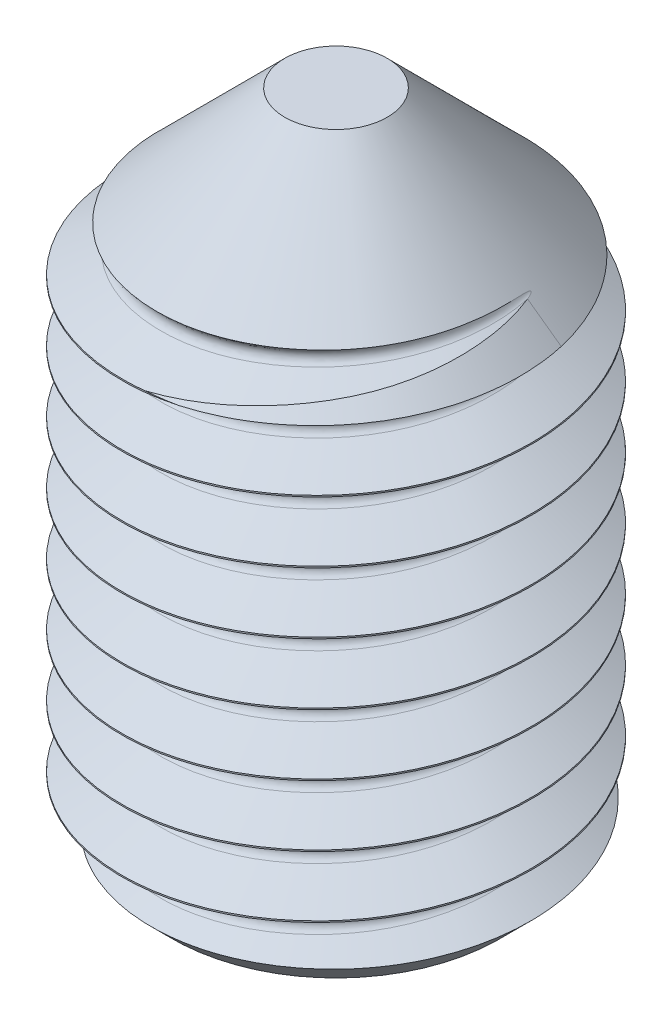
SolidWorks part; units mm, degrees
ref_plane "Front Plane" through (0, 0, 0) normal (0, 0, 1) x (1, 0, 0)
ref_plane "Top Plane" through (0, 0, 0) normal (0, 1, 0) x (1, 0, 0)
ref_plane "Right Plane" through (0, 0, 0) normal (1, 0, 0) x (0, 0, -1)
sketch "Sketch1" plane through (0, 0, 0) normal (0, 1, 0) x (1, 0, 0)
  circle A0 centre (0, 0) radius 5
  dimension "D1" = 10
extrude "Boss-Extrude1" add sketch "Sketch1" along normal mid plane 16
sketch "Sketch2" plane through (0, 0, 0) normal (0, 0, 1) x (1, 0, 0)
  line L0 (1.25, 8) -> (8.3582, 0.8918)
  line L1 (8.3582, 0.8918) -> (8.3582, -3.6418)
  line L2 (8.3582, -3.6418) -> (4, -8)
  line L3 (4, -8) -> (4, -11.4405)
  line L4 (4, -11.4405) -> (11.5714, -11.4405)
  line L5 (11.5714, -11.4405) -> (11.5714, 12.2044)
  line L6 (11.5714, 12.2044) -> (1.25, 12.2044)
  line L7 (1.25, 12.2044) -> (1.25, 8)
  line L8 (0, 0) -> (0, -3.1523) construction
  line L9 (5, 8) -> (-5, 8) construction
  line L10 (-5, -8) -> (5, -8) construction
  dimension "D1" = 2.5
  dimension "D2" = 8
  dimension "D3" = 135
  dimension "D4" = 135
revolve "Cut-Revolve1" cut sketch "Sketch2" angle 360 about L8
sketch "Sketch3" plane through (0, -8, 0) normal (0, -1, 0) x (1, 0, 0)
  line L1 (2.57, -1.4838) -> (2.57, 1.4838)
  line L2 (2.57, 1.4838) -> (0, 2.9676)
  line L3 (0, 2.9676) -> (-2.57, 1.4838)
  line L4 (-2.57, 1.4838) -> (-2.57, -1.4838)
  line L5 (-2.57, -1.4838) -> (0, -2.9676)
  line L6 (0, -2.9676) -> (2.57, -1.4838)
  circle A0 centre (0, 0) radius 2.57 construction
  dimension "D1" = 5.14
extrude "Cut-Extrude1" cut sketch "Sketch3" against normal blind 5
sketch "Sketch4" plane through (0, -8, 0) normal (0, -1, 0) x (1, 0, 0)
  circle A0 centre (0, 0) radius 5 construction
  circle A1 centre (0, 0) radius 5
curve "Helix/Spiral1" pitch 1.5 height 21.75 radius 5 centre (0, -8, 0) axis (0, 1, 0) start towards (0, 0, -1)
sketch "Sketch5" plane through (0, 0, 0) normal (0, 0, 1) x (1, 0, 0)
  line L1 (5.0292, -7.4079) -> (4.0554, -7.97)
  line L2 (4.0554, -8.3447) -> (5.0292, -8.9069)
  line L3 (5.0292, -8.9069) -> (5.0292, -7.4079)
  circle A0 centre (4.5964, -8.1574) radius 0.4327 construction
  arc A1 (4.0554, -7.97) -> (4.0554, -8.3447) centre (4.1636, -8.1574) ccw
  point P7 (4.7598, -8.2039)
  point P8 (4.5964, -8.1574)
  dimension "D2" = 0.2163
  dimension "D1" = 1.499
sweep "Cut-Sweep1" cut profiles "Sketch5" path "Helix/Spiral1" align with end faces yes
sketch "Sketch6" plane through (0, -8, 0) normal (0, -1, 0) x (1, 0, 0)
  circle A0 centre (0, 0) radius 2.9676
extrude "Cut-Extrude2" cut sketch "Sketch6" against normal blind 1.5 draft 75
